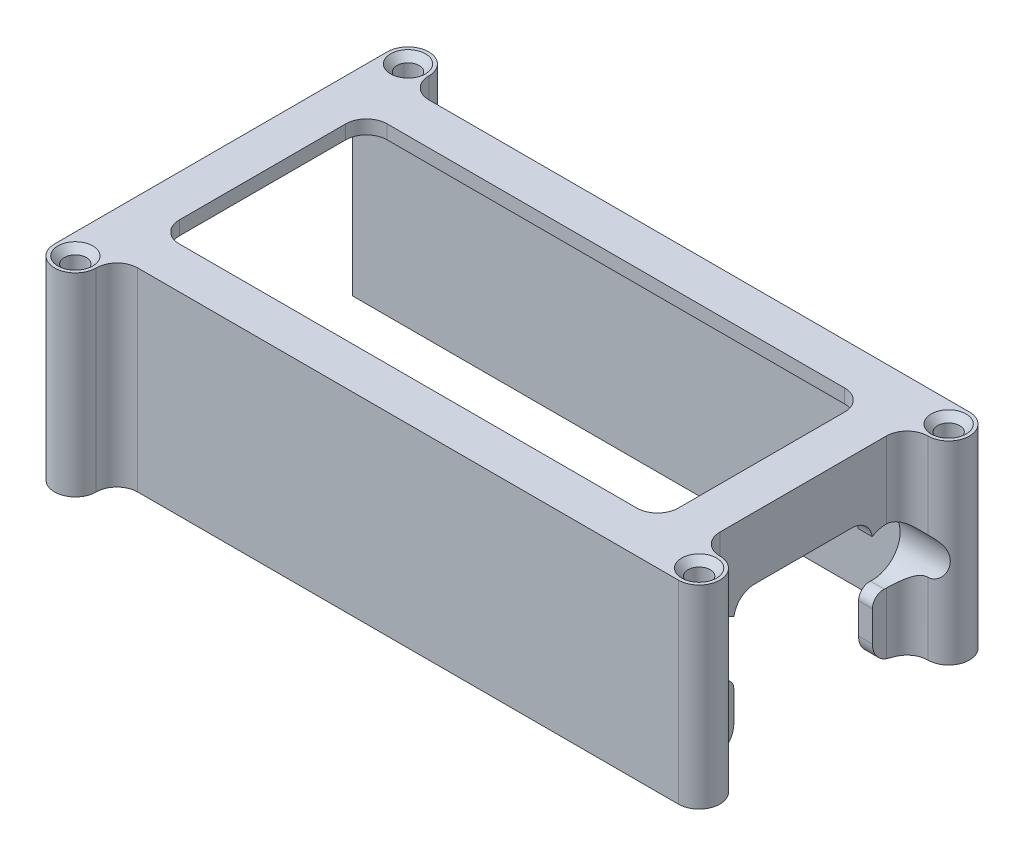
SolidWorks part; units mm, degrees
ref_plane "Front Plane" through (0, 0, 0) normal (0, 0, 1) x (1, 0, 0)
ref_plane "Top Plane" through (0, 0, 0) normal (0, 1, 0) x (1, 0, 0)
ref_plane "Right Plane" through (0, 0, 0) normal (1, 0, 0) x (0, 0, -1)
sketch "Sketch1" plane through (0, 0, 0) normal (0, 1, 0) x (1, 0, 0)
  line L0 (63.5, 30.1625) -> (66.675, 33.3375) construction
  line L1 (-63.5, -30.1625) -> (63.5, -30.1625)
  line L2 (-63.5, -30.1625) -> (-63.5, 30.1625)
  line L3 (-63.5, 30.1625) -> (63.5, 30.1625)
  line L4 (63.5, -30.1625) -> (63.5, 30.1625)
  line L5 (-63.5, -30.1625) -> (63.5, 30.1625) construction
  line L6 (-63.5, 30.1625) -> (63.5, -30.1625) construction
  line L7 (-66.675, -33.3375) -> (66.675, -33.3375)
  line L8 (-66.675, -33.3375) -> (-66.675, 33.3375)
  line L9 (-66.675, 33.3375) -> (66.675, 33.3375)
  line L10 (66.675, -33.3375) -> (66.675, 33.3375)
  line L11 (-66.675, -33.3375) -> (66.675, 33.3375) construction
  line L12 (-66.675, 33.3375) -> (66.675, -33.3375) construction
  line L13 (63.5, -30.1625) -> (66.675, -33.3375) construction
  point P0 (0, 0)
  point P6 (0, 0)
  dimension "D1" = 60.325
  dimension "D2" = 127
  dimension "D3" = 3.175
extrude "Boss-Extrude1" add sketch "Sketch1" along normal blind 41.275
sketch "Sketch2" plane through (-66.675, 0, 0) normal (-1, 0, 0) x (0, 0, 1)
  line L0 (-33.3375, 0) -> (33.3375, 0) construction
  line L1 (-15.875, -30.1625) -> (15.875, -30.1625)
  line L2 (-15.875, -30.1625) -> (-15.875, 30.1625)
  line L3 (-15.875, 30.1625) -> (15.875, 30.1625)
  line L4 (15.875, -30.1625) -> (15.875, 30.1625)
  line L5 (-15.875, -30.1625) -> (15.875, 30.1625) construction
  line L6 (-15.875, 30.1625) -> (15.875, -30.1625) construction
  point P0 (0, 0)
  dimension "D1" = 31.75
  dimension "D2" = 30.1625
extrude "Cut-Extrude1" cut sketch "Sketch2" against normal through all
sketch "Sketch3" plane through (0, 41.275, 0) normal (0, 1, 0) x (1, 0, 0)
  line L0 (-66.675, 33.3375) -> (-57.15, 23.8125) construction
  line L1 (57.15, -23.8125) -> (-57.15, -23.8125)
  line L2 (57.15, -23.8125) -> (57.15, 23.8125)
  line L3 (57.15, 23.8125) -> (-57.15, 23.8125)
  line L4 (66.675, -33.3375) -> (66.675, 33.3375)
  line L5 (66.675, 33.3375) -> (-66.675, 33.3375)
  line L6 (-66.675, 33.3375) -> (-66.675, -33.3375)
  line L7 (-66.675, -33.3375) -> (66.675, -33.3375)
  line L8 (66.675, -33.3375) -> (66.675, 33.3375)
  line L9 (66.675, 33.3375) -> (-66.675, 33.3375)
  line L10 (-66.675, 33.3375) -> (-66.675, -33.3375)
  line L11 (-66.675, -33.3375) -> (66.675, -33.3375)
  line L12 (-57.15, -23.8125) -> (-57.15, 23.8125)
  line L13 (57.15, -23.8125) -> (-57.15, 23.8125) construction
  line L14 (57.15, 23.8125) -> (-57.15, -23.8125) construction
  line L15 (-66.675, -33.3375) -> (-57.15, -23.8125) construction
  line L16 (63.5, 30.1625) -> (-63.5, 30.1625) construction
  point P2 (0, 0)
  dimension "D2" = 6.35
  dimension "D1" = 0
extrude "Boss-Extrude2" add sketch "Sketch3" along normal blind 3.175
sketch "Sketch4" plane through (0, 44.45, 0) normal (0, 1, 0) x (1, 0, 0)
  line L0 (66.675, -33.3375) -> (66.675, 33.3375) construction
  line L1 (71.4375, 33.3375) -> (66.675, 33.3375)
  line L2 (66.675, 33.3375) -> (66.675, 19.05)
  circle A0 centre (71.4375, 28.575) radius 1.27 construction
  arc A1 (71.4375, 33.3375) -> (71.4375, 23.8125) centre (71.4375, 28.575) cw
  arc A2 (66.675, 19.05) -> (71.4375, 23.8125) centre (71.4375, 19.05) cw
  dimension "D1" = 4.7625
  dimension "D2" = 2.54
extrude "Boss-Extrude3" add sketch "Sketch4" against normal up to surface (44.45 mm away) up to face at (0, 0, -23.8125)
ref_axis "Axis1" through (71.4375, 0, -28.575) along (0, 1, 0)
ref_plane "Plane1" through (71.4375, 0, 0) normal (1, 0, 0) x (0, 1, 0)
sketch "Sketch5" plane through (71.4375, 0, 0) normal (1, 0, 0) x (0, 1, 0)
  line L0 (0, -31.115) -> (42.8625, -31.115)
  line L1 (42.8625, -31.115) -> (44.45, -32.5697)
  line L2 (44.45, -33.3375) -> (44.45, -23.8125) construction
  line L3 (44.45, -32.5697) -> (44.45, -28.575)
  line L4 (44.45, -28.575) -> (0, -28.575) construction
  line L5 (0, -28.575) -> (44.45, -28.575) construction
  line L6 (0, -28.575) -> (0, -31.115)
  line L7 (0, -23.8125) -> (0, -33.3375) construction
  line L8 (44.45, -28.575) -> (0, -28.575)
  dimension "D1" = 5.08
  dimension "D2" = 42.5
  dimension "D3" = 1.5875
revolve "Cut-Revolve1" cut sketch "Sketch5" angle 360 about L8
sketch "Sketch6" plane through (0, 44.45, 0) normal (0, 1, 0) x (1, 0, 0)
  line L0 (-66.675, 33.3375) -> (-66.675, -33.3375) construction
  line L1 (-66.675, 38.1) -> (-66.675, 33.3375)
  line L2 (-66.675, 33.3375) -> (-52.3875, 33.3375)
  line L3 (71.4375, 33.3375) -> (-66.675, 33.3375) construction
  circle A0 centre (-61.9125, 38.1) radius 3.9947 construction
  arc A1 (-57.15, 38.1) -> (-66.675, 38.1) centre (-61.9125, 38.1) ccw
  arc A2 (-52.3875, 33.3375) -> (-57.15, 38.1) centre (-52.3875, 38.1) cw
  arc A3 (71.4375, 23.8125) -> (71.4375, 33.3375) centre (71.4375, 28.575) ccw construction
  circle A5 centre (71.4375, 28.575) radius 3.9947 construction
  arc A6 (-61.9125, 33.3375) -> (-57.15, 38.1) centre (-61.9125, 38.1) ccw construction
  arc A7 (-66.675, 38.1) -> (-61.9125, 33.3375) centre (-61.9125, 38.1) ccw construction
  circle A8 centre (-61.9125, 38.1) radius 2.54
  circle A9 centre (71.4375, 28.575) radius 2.54 construction
extrude "Boss-Extrude4" add sketch "Sketch6" against normal up to surface (44.45 mm away) up to face at (0, 0, 23.8125)
ref_axis "Axis2" through (-61.9125, 0, -38.1) along (0, 1, 0)
ref_plane "Plane2" through (-61.9125, 0, 0) normal (-1, 0, 0) x (0, 1, 0)
sketch "Sketch7" plane through (-61.9125, 0, 0) normal (-1, 0, 0) x (0, 1, 0)
  line L0 (42.8625, 40.64) -> (44.45, 42.0947)
  line L1 (0, 38.1) -> (44.45, 38.1) construction
  line L2 (44.45, 38.1) -> (44.45, 42.8625) construction
  line L3 (44.45, 42.0947) -> (44.45, 38.1)
  line L4 (44.45, 35.56) -> (44.45, 40.64) construction
  line L5 (44.45, 38.1) -> (42.8625, 38.1)
  line L6 (44.45, 32.5697) -> (42.8625, 31.115) construction
  line L7 (42.8625, 38.1) -> (42.8625, 40.64)
  line L8 (40.0906, 38.1) -> (42.8625, 40.64) construction
  line L9 (42.8625, 38.1) -> (40.0906, 38.1) construction
  line L10 (44.45, 28.575) -> (44.45, 32.5697) construction
  line L11 (0, 28.575) -> (44.45, 28.575) construction
  line L12 (44.45, 38.1) -> (44.45, -33.3375) construction
revolve "Cut-Revolve2" cut sketch "Sketch7" angle 360 about L9
mirror "Mirror1" about plane through (0, 0, 0) normal (0, 0, 1) of "Cut-Revolve2", "Boss-Extrude4", "Boss-Extrude3", "Cut-Revolve1"
mirror "Mirror2" [suppressed] about plane through (0, 0, 0) normal (1, 0, 0)
sketch "Sketch8" plane through (-63.5, 0, 0) normal (1, 0, 0) x (0, 0, -1)
  line L8 (-15.875, 0) -> (-15.875, 30.1625)
  line L9 (-15.875, 30.1625) -> (15.875, 30.1625)
  line L10 (15.875, 30.1625) -> (15.875, 0)
  line L11 (15.875, 0) -> (30.1625, 0)
  line L12 (30.1625, 0) -> (30.1625, 41.275)
  line L13 (30.1625, 41.275) -> (-30.1625, 41.275)
  line L14 (-30.1625, 41.275) -> (-30.1625, 0)
  line L15 (-30.1625, 0) -> (-15.875, 0)
  line L16 (-15.875, 0) -> (-15.875, 30.1625)
  line L17 (-15.875, 30.1625) -> (15.875, 30.1625)
  line L18 (15.875, 30.1625) -> (15.875, 0)
  line L19 (15.875, 0) -> (30.1625, 0)
  line L20 (30.1625, 0) -> (30.1625, 41.275)
  line L21 (30.1625, 41.275) -> (-30.1625, 41.275)
  line L22 (-30.1625, 41.275) -> (-30.1625, 0)
  line L23 (-30.1625, 0) -> (-15.875, 0)
  dimension "D1" = 0
extrude "Cut-Extrude2" cut sketch "Sketch8" against normal through all
fillet "Fillet1" radius 1.5875 5 edges at (63.5, 20.6375, -30.1625) (-1.5875, 41.275, -30.1625) (63.5, 20.6375, 30.1625) (63.5, 41.275, 0) (-1.5875, 41.275, 30.1625)
fillet "Fillet2" radius 4.7625 8 edges at (65.0875, 0, 15.875) (65.0875, 0, -15.875) (65.0875, 30.1625, -15.875) (65.0875, 30.1625, 15.875) (-57.15, 42.8625, 23.8125) (-57.15, 42.8625, -23.8125) (57.15, 42.8625, 23.8125) (57.15, 42.8625, -23.8125)
sketch "Sketch9" plane through (63.5, 0, 0) normal (-1, 0, 0) x (0, 0, 1)
  line L0 (-28.575, 41.275) -> (28.575, 41.275) construction
  line L1 (30.1625, 41.275) -> (-30.1625, 41.275) construction
  line L2 (30.1625, 41.275) -> (30.1625, 0) construction
  line L3 (30.1625, 0) -> (-30.1625, 0) construction
  line L4 (-30.1625, 41.275) -> (-30.1625, 0) construction
  line L5 (30.1625, 41.275) -> (-30.1625, 0) construction
  line L6 (30.1625, 0) -> (-30.1625, 41.275) construction
  line L7 (19.05, 20.6375) -> (-19.05, 20.6375) construction
  line L8 (25.4, 20.6375) -> (30.1625, 20.6375) construction
  circle A0 centre (19.05, 20.6375) radius 6.35
  circle A1 centre (-19.05, 20.6375) radius 6.35
  point P0 (0, 20.6375)
  point P13 (0, 20.6375)
  dimension "D1" = 12.7
  dimension "D2" = 4.7625
extrude "Cut-Extrude4" cut sketch "Sketch9" against normal through all
fillet "Fillet3" radius 2.54 2 edges at (65.0875, 15.1382, -15.875) (65.0875, 15.1382, 15.875)
